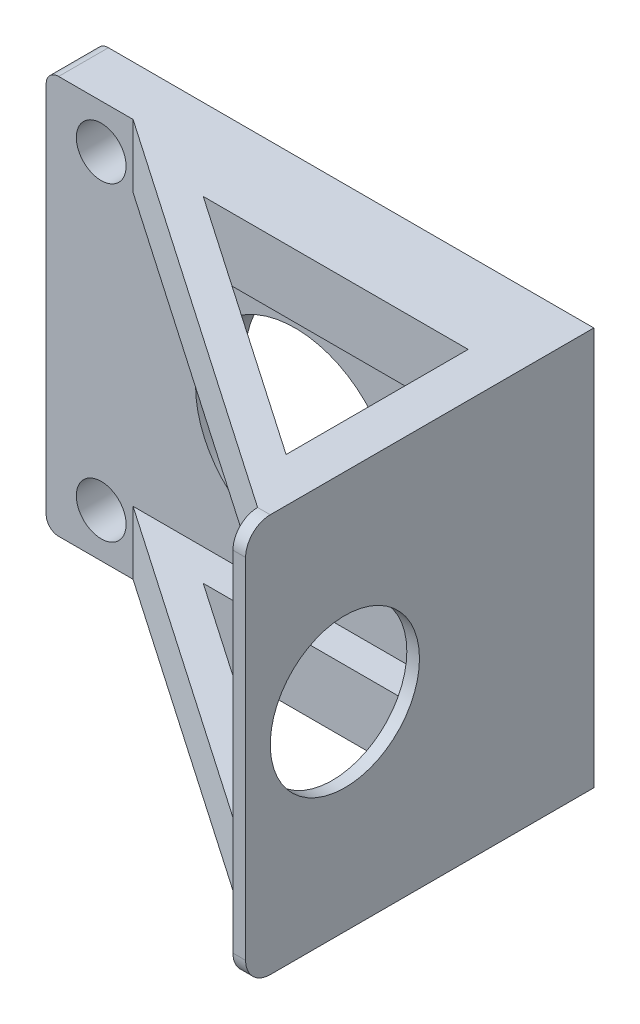
SolidWorks part; units mm, degrees
ref_plane "Front Plane" through (0, 0, 0) normal (0, 0, 1) x (1, 0, 0)
ref_plane "Top Plane" through (0, 0, 0) normal (0, 1, 0) x (1, 0, 0)
ref_plane "Right Plane" through (0, 0, 0) normal (1, 0, 0) x (0, 0, -1)
ref_plane "Plane1" through (0, 0, 20) normal (0, 0, 1) x (1, 0, 0)
sketch "Sketch1" plane through (0, 0, 20) normal (0, 0, 1) x (1, 0, 0)
  line L0 (95, 80) -> (-95, 80)
  line L1 (-100, 75) -> (-100, -75)
  line L2 (-95, -80) -> (95, -80)
  line L3 (100, -75) -> (100, 75)
  line L4 (95, -80) -> (100, -80)
  line L5 (100, -80) -> (100, -75)
  line L6 (95, 80) -> (100, 80)
  line L7 (100, 80) -> (100, 75)
  circle A0 centre (-77.8954, 62.3163) radius 10
  circle A1 centre (83.46, 0.37) radius 10
  circle A2 centre (-77.8954, -62.3163) radius 10
  circle A3 centre (0, 0) radius 40
  arc A4 (-95, 80) -> (-100, 75) centre (-95, 75) ccw
  arc A5 (-100, -75) -> (-95, -80) centre (-95, -75) ccw
extrude "Boss-Extrude1" add sketch "Sketch1" against normal blind 20
sketch "Sketch2" plane through (100, 0, 0) normal (1, 0, 0) x (0, 0, -1)
  line L0 (-20, -80) -> (-20, 80) construction
  line L1 (-20, 0) -> (-100.01, 0) construction
  line L2 (-20, -80) -> (-20, 80)
  line L3 (-20, 80) -> (-139.888, 80)
  line L4 (-139.888, 80) -> (-139.888, -80)
  line L5 (-139.888, -80) -> (-20, -80)
  line L6 (-100.01, 0) -> (-139.888, 0) construction
  circle A0 centre (-100.01, 0) radius 29.972
extrude "Boss-Extrude3" add sketch "Sketch2" against normal blind 5.08 contours L3 L4 L5 L2
sketch "Sketch3" plane through (100, 0, 0) normal (1, 0, 0) x (0, 0, -1)
  circle A0 centre (-100.01, 0) radius 29.972
extrude "Cut-Extrude1" cut sketch "Sketch2<7>" against normal through all contours A0
sketch "Sketch2<7>" plane through (100, 0, 0) normal (1, 0, 0) x (0, 0, -1) same geometry as "Sketch2"
fillet "Fillet1" radius 9.906 1 edges at (97.46, 80, 139.888)
fillet "Fillet2" radius 9.906 1 edges at (97.46, -80, 139.888)
sketch "Sketch4" plane through (0, -80, 0) normal (0, -1, 0) x (1, 0, 0)
  line L0 (94.92, 129.982) -> (94.92, 20)
  line L1 (94.92, 20) -> (-65.1, 20)
  line L2 (-95, 20) -> (94.92, 20) construction
  line L3 (-65.1, 20) -> (94.92, 129.982)
  line L4 (82.22, 32.7) -> (-24.2003, 32.7)
  line L5 (-24.2003, 32.7) -> (82.22, 105.8429)
  line L6 (82.22, 105.8429) -> (82.22, 32.7)
  dimension "D1" = 12.7
extrude "Boss-Extrude4" add sketch "Sketch4" against normal blind 25.4
sketch "Sketch5" plane through (0, 80, 0) normal (0, 1, 0) x (1, 0, 0)
  line L0 (94.92, -129.982) -> (94.92, -20)
  line L1 (94.92, -20) -> (-65.1, -20)
  line L2 (94.92, -20) -> (-95, -20) construction
  line L3 (-65.1, -20) -> (94.92, -129.982)
  line L4 (-24.2003, -32.7) -> (82.22, -105.8429)
  line L5 (82.22, -105.8429) -> (82.22, -32.7)
  line L6 (82.22, -32.7) -> (-24.2003, -32.7)
  dimension "D1" = 12.7
extrude "Boss-Extrude5" add sketch "Sketch5" against normal blind 25.4
